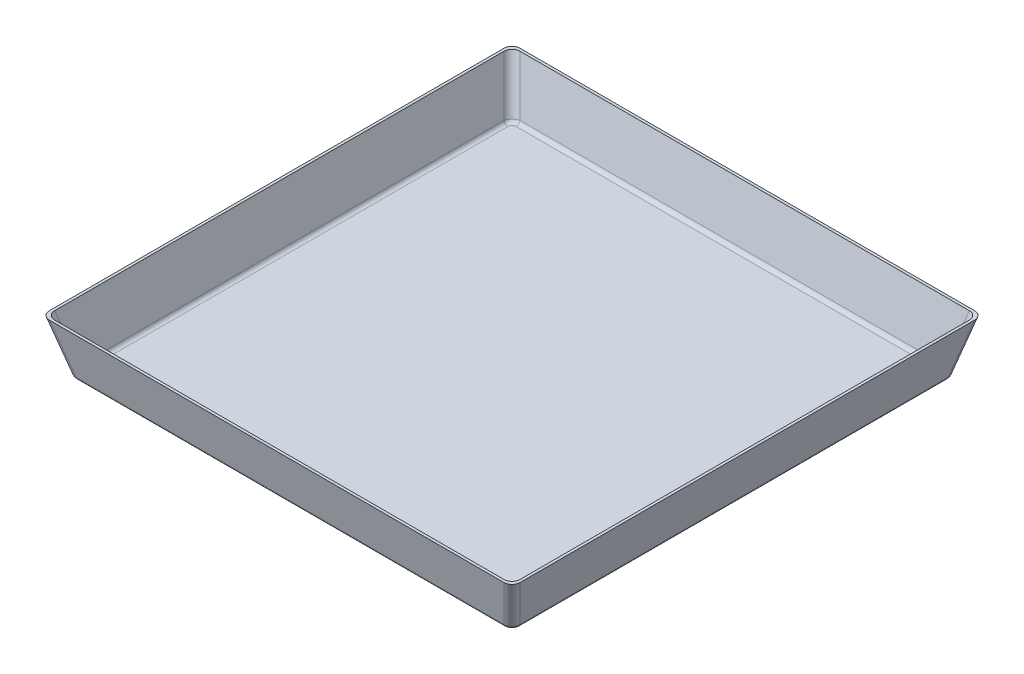
SolidWorks part; units mm, degrees
ref_plane "Front" through (0, 0, 0) normal (0, 0, 1) x (1, 0, 0)
ref_plane "Top" through (0, 0, 0) normal (0, 1, 0) x (1, 0, 0)
ref_plane "Right" through (0, 0, 0) normal (1, 0, 0) x (0, 0, -1)
sketch "Sketch1" plane through (0, 0, 0) normal (0, 1, 0) x (1, 0, 0)
  line L0 (0, 0) -> (266.7, 0)
  line L1 (266.7, 0) -> (266.7, 266.7)
  line L2 (266.7, 266.7) -> (0, 266.7)
  line L3 (0, 266.7) -> (0, 0)
extrude "Boss-Extrude1" add sketch "Sketch1" along normal blind 31.75 draft 15 draft outward yes
sketch "Sketch5" plane through (0, 31.75, 0) normal (0, 1, 0) x (1, 0, 0)
  line L8 (-6.9199, 273.6199) -> (-6.9199, -6.9199)
  line L9 (-6.9199, -6.9199) -> (273.6199, -6.9199)
  line L10 (273.6199, -6.9199) -> (273.6199, 273.6199)
  line L11 (273.6199, 273.6199) -> (-6.9199, 273.6199)
  line L12 (-6.9199, 273.6199) -> (-6.9199, -6.9199)
  line L13 (-6.9199, -6.9199) -> (273.6199, -6.9199)
  line L14 (273.6199, -6.9199) -> (273.6199, 273.6199)
  line L15 (273.6199, 273.6199) -> (-6.9199, 273.6199)
  dimension "D1" = 1.5875
extrude "Cut-Extrude3" cut sketch "Sketch5" against normal blind 30.353 draft 15
fillet "Fillet3" radius 5.08 4 edges at (269.5534, 16.5735, -269.5534) (269.5534, 16.5735, 2.8534) (-2.8534, 16.5735, -269.5534) (-2.8534, 16.5735, 2.8534)
fillet "Fillet4" radius 2.54 8 edges at (2.631, 1.397, -264.069) (133.35, 1.397, -265.4868) (264.069, 1.397, -264.069) (265.4868, 1.397, -133.35) (264.069, 1.397, -2.631) (133.35, 1.397, -1.2132) (2.631, 1.397, -2.631) (1.2132, 1.397, -133.35)
fillet "Fillet1" radius 5.08 4 edges at (-4.2537, 15.875, -270.9537) (270.9537, 15.875, -270.9537) (270.9537, 15.875, 4.2537) (-4.2537, 15.875, 4.2537)
fillet "Fillet2" radius 2.54 8 edges at (1.4178, 0, -265.2822) (133.35, 0, -266.7) (265.2822, 0, -265.2822) (266.7, 0, -133.35) (265.2822, 0, -1.4178) (133.35, 0, 0) (1.4178, 0, -1.4178) (0, 0, -133.35)
